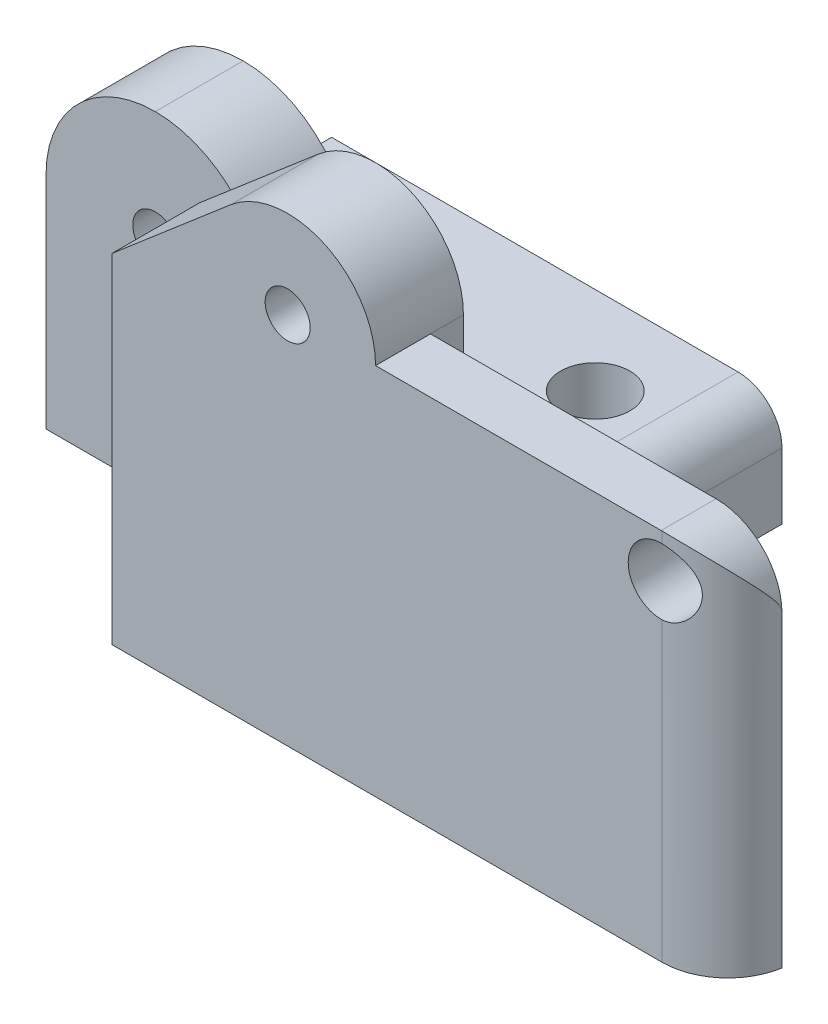
SolidWorks part; units mm, degrees
other "Marcação1"
sketch "Esboço27" plane through (-6, 21, 20) normal (-0.0417, 0.3861, 0.9215) x (0.9985, 0.0489, 0.0247)
ref_plane "Plano frontal" through (0, 0, 0) normal (0, 0, 1) x (1, 0, 0)
ref_plane "Plano superior" through (0, 0, 0) normal (0, 1, 0) x (1, 0, 0)
ref_plane "Plano direito" through (0, 0, 0) normal (1, 0, 0) x (0, 0, -1)
sketch "Esboço1" plane through (0, 0, 0) normal (0, 0, 1) x (1, 0, 0)
  line L0 (0, 0) -> (0, 12)
  line L1 (0, 12) -> (9.4001, 20.0398)
  line L4 (16, 17) -> (16, 4)
  line L5 (16, 4) -> (16, 0)
  line L6 (16, 0) -> (0, 0)
  arc A0 (9.4001, 20.0398) -> (16, 17) centre (12, 17) cw
  point P19 (12, 17)
  dimension "D1" = 4
  dimension "D2" = 16
  dimension "D3" = 12
  dimension "D4" = 16
  dimension "D5" = 4
  dimension "D6" = 17
extrude "Ressalto-extrusão1" add sketch "Esboço1" along normal blind 20
sketch "Esboço2" plane through (16, 0, 0) normal (1, 0, 0) x (0, 0, -1)
  line L0 (-20, 0) -> (-20, 5) construction
  line L1 (-20, 5) -> (0, 5) construction
  line L4 (0, 5) -> (-16, 5)
  line L5 (0, 5) -> (0, 21)
  line L6 (0, 21) -> (-16, 21)
  line L7 (-16, 5) -> (-16, 21)
  line L8 (0, 21) -> (-20, 21) construction
  line L9 (0, 0) -> (0, 17) construction
  dimension "D1" = 16
  dimension "D2" = 5
extrude "Corte-extrusão1" cut sketch "Esboço2" against normal blind 20
sketch "Esboço3" plane through (0, 0, 20) normal (0, 0, 1) x (1, 0, 0)
  line L0 (0, 0) -> (4, 0)
  line L1 (0, 0) -> (16, 0) construction
  line L2 (4, 0) -> (4, 15.4212)
  line L3 (9.4001, 20.0398) -> (0, 12) construction
  line L4 (4, 15.4212) -> (0, 12)
  line L5 (0, 12) -> (0, 0)
  dimension "D1" = 4
extrude "Corte-extrusão2" cut sketch "Esboço3" against normal through all
sketch "Esboço8" plane through (4, 0, 0) normal (-1, 0, 0) x (0, 0, 1)
  line L0 (0, 5) -> (13, 5)
  line L1 (0, 5) -> (16, 5) construction
  line L2 (13, 5) -> (13, 0)
  line L3 (0, 0) -> (20, 0) construction
  line L4 (13, 0) -> (0, 0)
  line L5 (0, 0) -> (0, 5)
  dimension "D1" = 13
extrude "Ressalto-extrusão2" add sketch "Esboço8" along normal blind 10
sketch "Esboço9" plane through (0, 0, 0) normal (0, -1, 0) x (1, 0, 0)
  line L0 (10, 20) -> (10, 0) construction
  line L1 (4, 20) -> (16, 20) construction
  line L2 (-6, 0) -> (16, 0) construction
  line L3 (-6, 4) -> (10, 4) construction
  line L5 (10, 4) -> (16, 4) construction
  line L6 (16, 20) -> (16, 0) construction
  line L7 (-6, 0) -> (-6, 13) construction
  line L8 (16, 20) -> (16, 0) construction
  point P10 (10, 14)
  point P15 (4, 4)
  point P16 (-2, 4)
  point P23 (10, 9)
  dimension "D1" = 18
  dimension "D2" = 6
  dimension "D3" = 6
  dimension "D4" = 5
  dimension "D5" = 4
hole_wizard "Furo roscado para conduíte de M3x0.51" positions "3DSketch2" profile "Esboço10" tap size "M3x0.5" standard "Helicoil® Metric" end condition through all
sketch3d "3DSketch2"
  point P0 (-2, 0, 4)
  point P6 (10, 0, 4)
  point P12 (10, 0, 14)
cosmetic thread "Rosca de furo2" parameters "D1"=10, "D2"=3.716
cosmetic thread "Rosca de furo4" parameters "D1"=10, "D2"=3.716
cosmetic thread "Rosca de furo6" parameters "D1"=10, "D2"=3.716
sketch "Esboço10" plane through (-2, 0, 4) normal (1, 0, 0) x (0, 0, -1)
  line L0 (0, 0) -> (0, 21)
  line L1 (0, 21) -> (1.575, 21)
  line L2 (1.575, 21) -> (1.575, 0)
  line L5 (1.575, 0) -> (0, 0)
  line L11 (0, -6.35) -> (0, 107.95) construction
  dimension "Thru Tap Drill Dia." = 3.15
  dimension "Thru Tap Drill Depth" = 21
sketch "Esboço20" plane through (0, 5, 0) normal (0, 1, 0) x (1, 0, 0)
  line L1 (-6, -13) -> (3.95, -13)
  line L2 (-6, -13) -> (-6, -9)
  line L3 (-6, -9) -> (3.95, -9)
  line L4 (3.95, -13) -> (3.95, -9)
  dimension "D1" = 0.05
  dimension "D2" = 4
extrude "Ressalto-extrusão6" add sketch "Esboço20" along normal blind 10
fillet "Filete3" radius 4.975 2 edges at (3.95, 15, 11) (-6, 15, 11)
hole_wizard "Broca de rosquear para tarraxa de M2.54" positions "Esboço21" profile "Esboço23" hole size "M2.5" standard "ISO" end condition up to next
sketch "Esboço21" plane through (0, 0, 13) normal (0, 0, 1) x (1, 0, 0)
  point P0 (-1.025, 10.025)
sketch "Esboço23" plane through (-1.025, 10.025, 13) normal (1, 0, 0) x (0, -1, 0)
  line L0 (0, 0) -> (0, 4)
  line L1 (0, 4) -> (1.025, 4)
  line L2 (1.025, 4) -> (1.025, 0)
  line L5 (1.025, 0) -> (0, 0)
  line L11 (0, -6.35) -> (0, 107.95) construction
  dimension "Thru Hole Dia." = 2.05
  dimension "Thru Hole Depth" = 4
sketch "Esboço24" plane through (0, 5, 0) normal (0, 1, 0) x (1, 0, 0)
  line L0 (16, -16) -> (9.4001, -16) construction
  line L1 (16, 0) -> (14.5, 0)
  line L2 (16, 0) -> (16, -16)
  line L3 (16, -16) -> (14.5, -16)
  line L4 (14.5, 0) -> (14.5, -16)
  dimension "D1" = 1.5
extrude "Corte-extrusão3" cut sketch "Esboço24" against normal through all
fillet "Filete5" radius 2 1 edges at (14.5, 5, 8)
hole_wizard "Broca de rosquear para tarraxa de M2.55" positions "Esboço28" profile "Esboço29" hole size "M2.5" standard "ISO" end condition up to next
sketch "Esboço28" plane through (0, 0, 20) normal (0, 0, 1) x (1, 0, 0)
  line L0 (9.4001, 20.0398) -> (12, 17) construction
  point P0 (12, 17)
sketch "Esboço29" plane through (12, 17, 20) normal (1, 0, 0) x (0, -1, 0)
  line L0 (0, 0) -> (0, 4)
  line L1 (0, 4) -> (1.025, 4)
  line L2 (1.025, 4) -> (1.025, 0)
  line L5 (1.025, 0) -> (0, 0)
  line L11 (0, -6.35) -> (0, 107.95) construction
  dimension "Thru Hole Dia." = 2.05
  dimension "Thru Hole Depth" = 4
sketch "Esboço30" plane through (16, 0, 0) normal (1, 0, 0) x (0, 0, -1)
  line L0 (-20, 17) -> (-16, 17) construction
  line L1 (-20, 0) -> (-17.5, 0)
  line L2 (-20, 0) -> (-20, 17)
  line L3 (-20, 17) -> (-17.5, 17)
  line L4 (-17.5, 0) -> (-17.5, 17)
  dimension "D1" = 2.5
extrude "Ressalto-extrusão9" add sketch "Esboço30" along normal blind 16
fillet "Filete12" radius 3 2 edges at (32, 17, 18.75) (32, 8.5, 20)
sketch "Esboço31" plane through (0, 0, 20) normal (0, 0, 1) x (1, 0, 0)
  line L0 (29, 17) -> (16, 17) construction
  line L1 (32, 0) -> (32, 14) construction
  circle A0 centre (29, 15) radius 1.5
  dimension "D1" = 3
  dimension "D2" = 2
  dimension "D3" = 3
extrude "Corte-extrusão4" cut sketch "Esboço31" against normal through all
